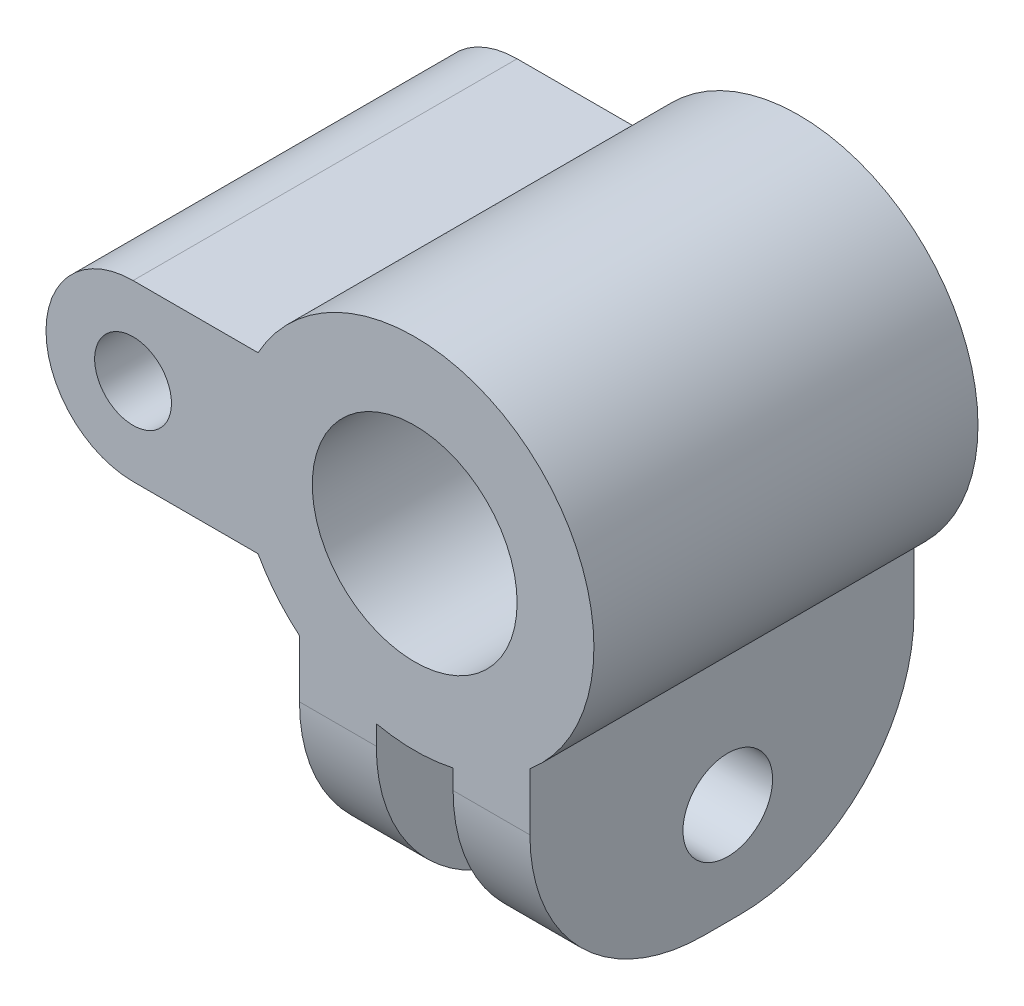
SolidWorks part; units mm, degrees
ref_plane "Front Plane" through (0, 0, 0) normal (0, 0, 1) x (1, 0, 0)
ref_plane "Top Plane" through (0, 0, 0) normal (0, 1, 0) x (1, 0, 0)
ref_plane "Right Plane" through (0, 0, 0) normal (1, 0, 0) x (0, 0, -1)
sketch "Sketch1" plane through (0, 0, 0) normal (0, 0, 1) x (1, 0, 0)
  line L0 (-55, 7.5) -> (-34.187, 7.5)
  line L1 (-55, -7.5) -> (-34.187, -7.5)
  line L2 (-55, 17) -> (-30.5941, 17)
  line L3 (-55, -17) -> (-30.5941, -17)
  line L4 (0, 0) -> (0, -114.6684) construction
  line L5 (-7.5, -72) -> (-7.5, -34.187)
  line L7 (-22.5, -26.8095) -> (-22.5, -72)
  line L8 (-22.5, -72) -> (-7.5, -72)
  line L9 (7.5, -72) -> (7.5, -34.187)
  line L11 (22.5, -26.8095) -> (22.5, -72)
  line L12 (22.5, -72) -> (7.5, -72)
  circle A0 centre (0, 0) radius 20
  circle A1 centre (0, 0) radius 35
  circle A2 centre (-55, 0) radius 7.5
  arc A3 (-55, 17) -> (-55, -17) centre (-55, 0) ccw
  dimension "D1" = 70
  dimension "D2" = 40
  dimension "D3" = 15
  dimension "D4" = 17
  dimension "D5" = 55
  dimension "D6" = 15
  dimension "D7" = 15
  dimension "D8" = 7.5
  dimension "D9" = 7.5
  dimension "D10" = 72
  dimension "D11" = 72
extrude "Boss-Extrude1" add sketch "Sketch1" along normal blind 75 contours A0 A1 | L2 A3 L3 A1 L1 A2 L0 | A2 L1 A1 L0 region at (-63.0358, 0, 0) region at (-42.0153, 0, 0) region at (-31.811, 12.0308, 0)
extrude "Boss-Extrude2" add sketch "Sketch1<12>" along normal blind 75 contours A1 L9 L12 L11 | A1 L7 L8 L5 region at (15.223, -51.571, 0) region at (-15.223, -51.571, 0)
sketch "Sketch1<12>" plane through (0, 0, 0) normal (0, 0, 1) x (1, 0, 0) same geometry as "Sketch1"
fillet "Fillet6" radius 34 2 edges at (-15, -72, 0) (-15, -72, 75)
fillet "Fillet8" radius 34 2 edges at (15, -72, 0) (15, -72, 75)
sketch "Sketch3" plane through (22.5, 0, 0) normal (1, 0, 0) x (0, 0, -1)
  circle A0 centre (-36.3631, -52.2464) radius 8.7503
extrude "Cut-Extrude1" cut sketch "Sketch3" against normal blind 15
mirror "Mirror2" about plane through (0, 0, 0) normal (1, 0, 0) of "Cut-Extrude1"
